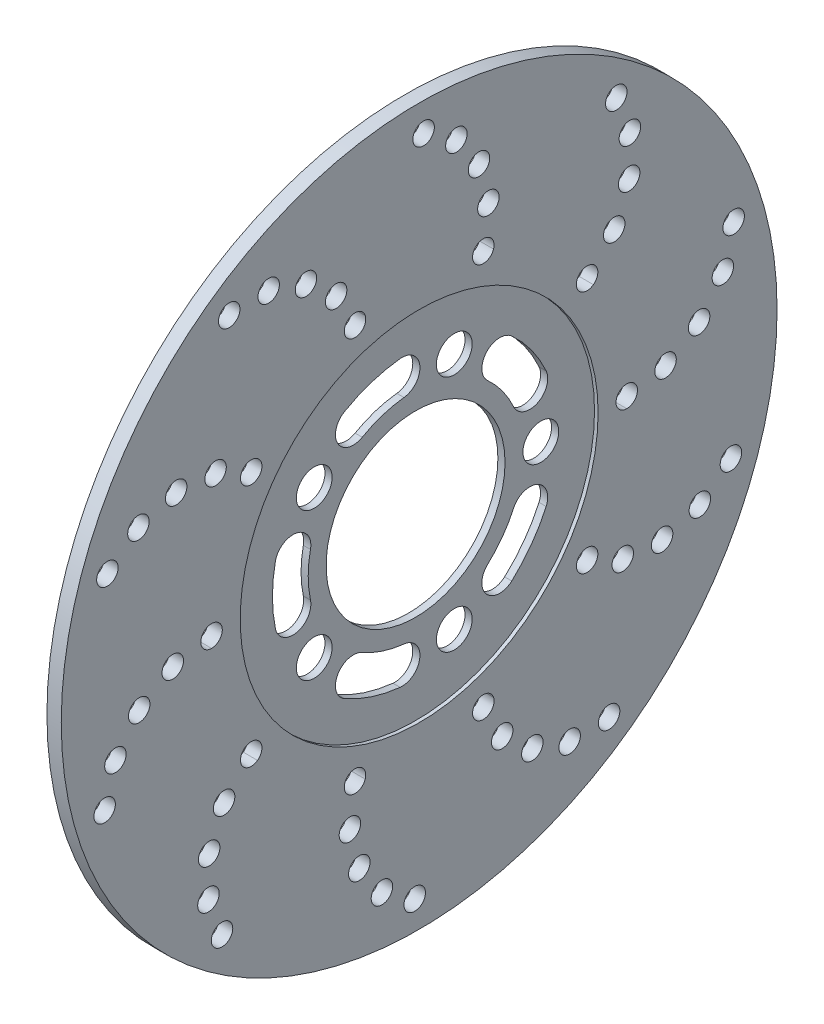
SolidWorks part; units mm, degrees
material "AISI 304"
ref_plane "Front Plane" through (0, 0, 0) normal (1, 0, 0) x (0, 1, 0)
ref_plane "Top Plane" through (0, 0, 0) normal (0, 0, 1) x (0, 1, 0)
ref_plane "Right Plane" through (0, 0, 0) normal (0, 1, 0) x (-1, 0, 0)
sketch "Sketch1" plane through (0, 0, 0) normal (1, 0, 0) x (0, 1, 0)
  line L0 (-112.8184, 0) -> (148.4018, 0) construction
  line L1 (0, 127.9014) -> (0, -119.9572) construction
  line L2 (0, 0) -> (-15.6118, 42.893) construction
  line L3 (0, 0) -> (15.2469, 41.8904) construction
  circle A0 centre (0, 0) radius 100
  circle A1 centre (0, 0) radius 50
  circle A3 centre (0, 0) radius 25
  circle A4 centre (0, -35) radius 5
  arc A5 (-40, 0) -> (40, 0) centre (0, 0) ccw
  arc A6 (6.1281, 29.3674) -> (-6.1281, 29.3674) centre (0, 0) ccw
  arc A7 (6.1281, 29.3674) -> (8.1708, 39.1566) centre (7.1495, 34.262) ccw
  arc A8 (-8.1708, 39.1566) -> (-6.1281, 29.3674) centre (-7.1495, 34.262) ccw
  arc A9 (-13.6808, 37.5877) -> (-40, 0) centre (0, 0) ccw construction
  arc A10 (8.1708, 39.1566) -> (-8.1708, 39.1566) centre (0, 0) ccw
  arc A11 (40, 0) -> (13.6808, 37.5877) centre (0, 0) ccw construction
  arc A12 (30, 0) -> (10.2606, 28.1908) centre (0, 0) ccw construction
  arc A13 (-30, 0) -> (30, 0) centre (0, 0) ccw
  arc A14 (-10.2606, 28.1908) -> (-30, 0) centre (0, 0) ccw construction
  arc A15 (-8.1708, 39.1566) -> (-13.6808, 37.5877) centre (0, 0) ccw construction
  arc A16 (13.6808, 37.5877) -> (8.1708, 39.1566) centre (0, 0) ccw construction
  arc A17 (10.2606, 28.1908) -> (6.1281, 29.3674) centre (0, 0) ccw construction
  arc A18 (-6.1281, 29.3674) -> (-10.2606, 28.1908) centre (0, 0) ccw construction
  dimension "D1" = 200
  dimension "D2" = 100
  dimension "D3" = 50
  dimension "D5" = 10
  dimension "D6" = 80
  dimension "D7" = 60
  dimension "D8" = 20
  dimension "D4" = 35
  dimension "D9" = 20
extrude "Boss-Extrude1" add sketch "Sketch1" along normal mid plane 4 contours A0 | A1
extrude "Boss-Extrude2" add sketch "Sketch1<3>" along normal mid plane 2 contours A1 A10 A7 A6 A8 A4 A3 | A4 | A6 A8 A10 A7 region at (0, -48.5858, 0)
sketch "Sketch1<3>" plane through (0, 0, 0) normal (1, 0, 0) x (0, 1, 0) same geometry as "Sketch1"
extrude "Cut-Extrude1" cut sketch "Sketch1<4>" against normal through all both and the other way through all contours A7 A10 A8 A6 | A4 region at (0, 0, -35) region at (0, 0, 34.5801)
sketch "Sketch1<4>" plane through (0, 0, 0) normal (1, 0, 0) x (0, 1, 0) same geometry as "Sketch1"
pattern_circular "CirPattern1" count 5 over 360 about axis through (1, 0, 0) along (1, 0, 0) of "Cut-Extrude1"
sketch "Sketch2" plane through (2, 0, 0) normal (1, 0, 0) x (0, 1, 0)
  line L0 (0, 88.2687) -> (0, -78.0626) construction
  line L1 (-110.3359, 0) -> (113.646, 0) construction
  line L2 (-27.2451, 87.8732) -> (-30.4284, 53.355) construction
  line L3 (0, 58) -> (-34.127, 58) construction
  circle A0 centre (0, 58) radius 3
  circle A1 centre (0, 0) radius 92 construction
  circle A2 centre (0, 0) radius 58 construction
  arc A3 (0, 58) -> (-27.2451, 87.8732) centre (-30, 58) ccw
  circle A4 centre (-27.2451, 87.8732) radius 3
  arc A5 (-2.027, 47.1598) -> (-16.6368, 84.8594) centre (-30, 58) ccw
  circle A6 centre (-16.6368, 84.8594) radius 3
  arc A7 (-7.834, 37.7845) -> (-7.8344, 78.2159) centre (-30, 58) ccw
  circle A8 centre (-7.8344, 78.2159) radius 3
  arc A9 (-16.6363, 31.1409) -> (-2.0272, 68.8407) centre (-30, 58) ccw
  circle A10 centre (-2.0272, 68.8407) radius 3
  arc A11 (-27.2445, 28.1268) -> (0, 58.0006) centre (-30, 58) ccw
  circle A12 centre (0, 58.0006) radius 3
  dimension "D1" = 6
  dimension "D2" = 58
  dimension "D3" = 184
  dimension "D4" = 116
  dimension "D5" = 30
  dimension "D6" = 6
  dimension "D7" = 5
  dimension "D8" = 11.0286
extrude "Cut-Extrude2" cut sketch "Sketch2" against normal through all both and the other way through all contours A4 | A5 A6 A3 | A3 A6 A5 | A7 A8 A5 | A5 A8 A7 | A9 A10 A7 | A7 A10 A9 | A11 A12 A0 A9 A3 | A0 A12 A11 A3 A9 region at (2, 1.2458, 58.0003) region at (2, -30.1529, 88.08) region at (2, -17.2158, 83.6956) region at (2, -16.0819, 85.9748) region at (2, -8.7948, 77.34) region at (2, -6.9139, 79.0555) region at (2, -3.2392, 68.371) region at (2, -0.8655, 69.2909) region at (2, -1.2998, 58.0003)
pattern_circular "CirPattern2" count 10 over 360 about axis through (2, 0, 0) along (1, 0, 0) of "Cut-Extrude2"
